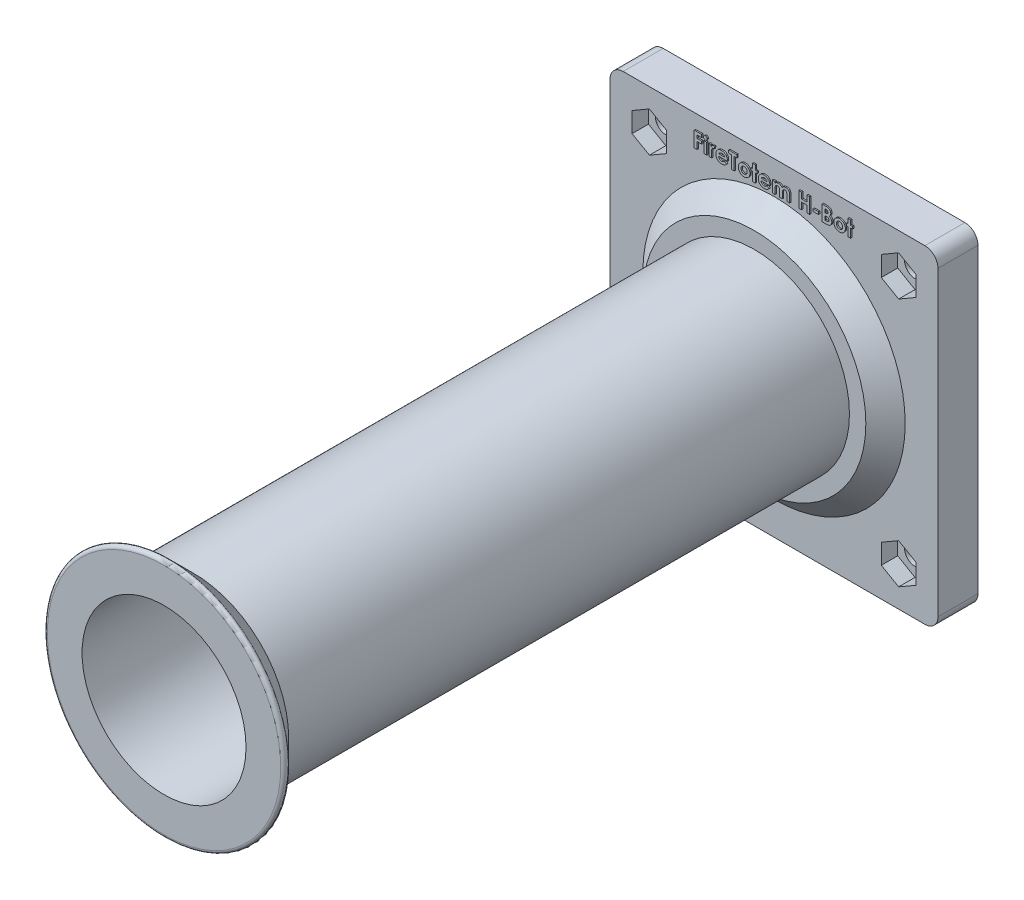
SolidWorks part; units mm, degrees
material "Настроенная пользователем пластмасса"
ref_plane "Front" through (0, 0, 0) normal (0, 0, 1) x (1, 0, 0)
ref_plane "Top" through (0, 0, 0) normal (0, 1, 0) x (1, 0, 0)
ref_plane "Right" through (0, 0, 0) normal (1, 0, 0) x (0, 0, -1)
sketch "Эскиз1" plane through (0, 0, 0) normal (0, 0, 1) x (1, 0, 0)
  line L1 (-23, 25) -> (23, 25)
  line L2 (-25, 23) -> (-25, -23)
  line L3 (-23, -25) -> (23, -25)
  line L4 (25, 23) -> (25, -23)
  line L5 (-25, 25) -> (25, -25) construction
  line L6 (-25, -25) -> (25, 25) construction
  circle A0 centre (-19, 19) radius 1.6
  circle A1 centre (19, 19) radius 1.6
  circle A2 centre (19, -19) radius 1.6
  circle A3 centre (-19, -19) radius 1.6
  arc A4 (-25, -23) -> (-23, -25) centre (-23, -23) ccw
  arc A5 (23, -25) -> (25, -23) centre (23, -23) ccw
  arc A6 (25, 23) -> (23, 25) centre (23, 23) ccw
  arc A7 (-23, 25) -> (-25, 23) centre (-23, 23) ccw
  circle A8 centre (0, 0) radius 12.5
  point P0 (0, 0)
  dimension "D3" = 3.2
  dimension "D4" = 3.2
  dimension "D5" = 3.2
  dimension "D6" = 3.2
  dimension "D7" = 6
  dimension "D8" = 38
  dimension "D9" = 6
  dimension "D10" = 38
  dimension "D11" = 38
  dimension "D12" = 2
  dimension "D13" = 25
  dimension "D1" = 50
  dimension "D2" = 50
extrude "Бобышка-Вытянуть1" add sketch "Эскиз1" along normal blind 6.1
sketch "Эскиз2" plane through (0, 0, 6.1) normal (0, 0, 1) x (1, 0, 0)
  line L1 (-19, 15.95) -> (-16.3586, 17.475)
  line L2 (-16.3586, 17.475) -> (-16.3586, 20.525)
  line L3 (-16.3586, 20.525) -> (-19, 22.05)
  line L4 (-19, 22.05) -> (-21.6414, 20.525)
  line L5 (-21.6414, 20.525) -> (-21.6414, 17.475)
  line L6 (-21.6414, 17.475) -> (-19, 15.95)
  line L7 (-19, -22.05) -> (-16.3586, -20.525)
  line L8 (-16.3586, -20.525) -> (-16.3586, -17.475)
  line L9 (-16.3586, -17.475) -> (-19, -15.95)
  line L10 (-19, -15.95) -> (-21.6414, -17.475)
  line L11 (-21.6414, -17.475) -> (-21.6414, -20.525)
  line L12 (-21.6414, -20.525) -> (-19, -22.05)
  line L13 (19, 15.95) -> (21.6414, 17.475)
  line L14 (21.6414, 17.475) -> (21.6414, 20.525)
  line L15 (21.6414, 20.525) -> (19, 22.05)
  line L16 (19, 22.05) -> (16.3586, 20.525)
  line L17 (16.3586, 20.525) -> (16.3586, 17.475)
  line L18 (16.3586, 17.475) -> (19, 15.95)
  line L19 (19, -22.05) -> (21.6414, -20.525)
  line L20 (21.6414, -20.525) -> (21.6414, -17.475)
  line L21 (21.6414, -17.475) -> (19, -15.95)
  line L22 (19, -15.95) -> (16.3586, -17.475)
  line L23 (16.3586, -17.475) -> (16.3586, -20.525)
  line L24 (16.3586, -20.525) -> (19, -22.05)
  circle A0 centre (-19, 19) radius 3.05 construction
  circle A1 centre (-19, -19) radius 3.05 construction
  circle A2 centre (19, 19) radius 3.05 construction
  circle A3 centre (19, -19) radius 3.05 construction
extrude "Вырез-Вытянуть1" cut sketch "Эскиз2" against normal blind 2.5
sketch "Эскиз3" plane through (0, 0, 6.1) normal (0, 0, 1) x (1, 0, 0)
  circle A0 centre (0, 0) radius 20
  dimension "D1" = 40
extrude "Бобышка-Вытянуть2" add sketch "Эскиз3" along normal blind 3
sketch "Эскиз4" plane through (0, 0, 9.1) normal (0, 0, 1) x (1, 0, 0)
  circle A0 centre (0, 0) radius 14.5
  dimension "D1" = 29
extrude "Бобышка-Вытянуть3" add sketch "Эскиз4" along normal blind 85
sketch "Эскиз5" plane through (0, 0, 94.1) normal (0, 0, 1) x (1, 0, 0)
  circle A0 centre (0, 0) radius 20
  dimension "D1" = 40
extrude "Бобышка-Вытянуть4" add sketch "Эскиз5" along normal blind 5
sketch "Эскиз6" plane through (0, 0, 99.1) normal (0, 0, 1) x (1, 0, 0)
  circle A0 centre (0, 0) radius 12.5
  dimension "D1" = 25
extrude "Вырез-Вытянуть2" cut sketch "Эскиз6" against normal through all
chamfer "Фаска1" distance 3 angle 45 1 edges at (20, 0, 9.1)
chamfer "Фаска2" distance 6 angle 45 1 edges at (20, 0, 94.1)
fillet "Скругление1" radius 0.5 1 edges at (19, 0, 99.1)
sketch "Эскиз7" plane through (0, 0, 6.1) normal (0, 0, 1) x (1, 0, 0)
  line L0 (-16.3586, 20.525) -> (16.2293, 20.525) construction
  line L1 (-16.3586, 17.475) -> (-16.3586, 20.525) construction
  text T0 "<b>FireTotem H-Bot</b>" font "Century Gothic" height 2.35
extrude "Бобышка-Вытянуть5" add sketch "Эскиз7" along normal blind 0.2
